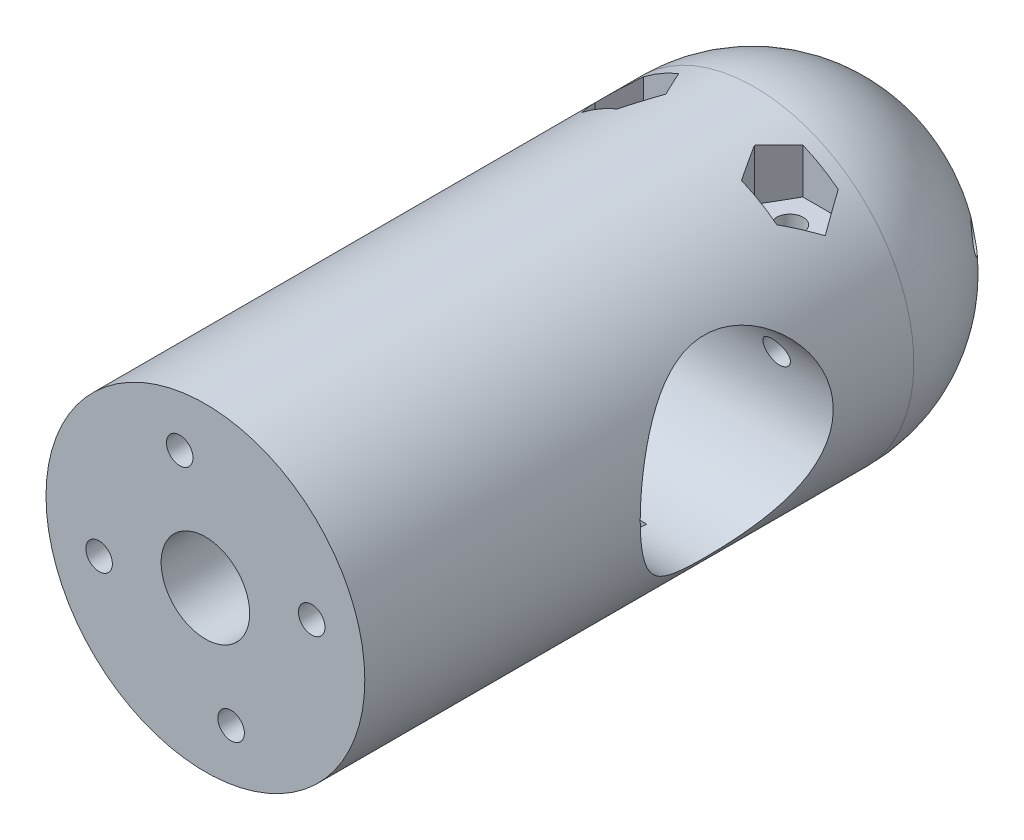
SolidWorks part; units mm, degrees
material "Custom Plastic"
ref_plane "Front Plane" through (0, 0, 0) normal (0, 0, 1) x (1, 0, 0)
ref_plane "Top Plane" through (0, 0, 0) normal (0, 1, 0) x (1, 0, 0)
ref_plane "Right Plane" through (0, 0, 0) normal (1, 0, 0) x (0, 0, -1)
sketch "Sketch1" plane through (0, 0, 0) normal (0, 0, 1) x (1, 0, 0)
  circle A0 centre (0, 0) radius 18
  dimension "D1" = 36
extrude "Boss-Extrude1" add sketch "Sketch1" along normal blind 62 contours A0
sketch "Sketch10" plane through (0, 0, 0) normal (0, 0, -1) x (-1, 0, 0)
  circle A0 centre (0, 0) radius 18
extrude "Boss-Extrude2" add sketch "Sketch10" along normal blind 17.5
fillet "Fillet1" radius 17.5 1 edges at (-18, 0, -17.5)
sketch "Sketch3" plane through (0, 0, 0) normal (1, 0, 0) x (0, 0, -1)
  line L0 (0, 0) -> (-62, 0) construction
  line L1 (-62, 18) -> (-62, -18) construction
  circle A0 centre (-20, 0) radius 10.9
  dimension "D2" = 21.8
  dimension "D1" = 20
extrude "Cut-Extrude1" cut sketch "Sketch3" against normal through all and the other way through all
sketch "Sketch4" plane through (0, 0, 62) normal (0, 0, 1) x (1, 0, 0)
  line L0 (0, 18) -> (0, -18) construction
  line L1 (18, 0) -> (-18, 0) construction
  circle A1 centre (0, 0) radius 18 construction
  circle A7 centre (12.0047, 2.9) radius 1.5
  circle A8 centre (2.9, -12.0047) radius 1.5
  circle A9 centre (-12.0047, -2.9) radius 1.5
  circle A10 centre (-2.9, 12.0047) radius 1.5
  point P10 (0, 0)
  point P19 (0, 0)
  dimension "D2" = 12.35
  dimension "D1" = 3
  dimension "D4" = 4
  dimension "D3" = 2.9
extrude "Cut-Extrude3" cut sketch "Sketch4" against normal through all contours A7 | A10 | A9 | A8
ref_plane "Plane1" through (0, -17.5, 0) normal (0, -1, 0) x (-1, 0, 0)
sketch "Sketch5" plane through (0, 0, 0) normal (0, 1, 0) x (1, 0, 0)
  line L1 (5, -5) -> (7, -8.4641)
  line L2 (7, -8.4641) -> (11, -8.4641)
  line L3 (11, -8.4641) -> (13, -5)
  line L4 (13, -5) -> (11, -1.5359)
  line L5 (11, -1.5359) -> (7, -1.5359)
  line L6 (7, -1.5359) -> (5, -5)
  line L7 (0, 0) -> (0, -62) construction
  line L8 (-18, -62) -> (18, -62) construction
  line L9 (-7, -1.5359) -> (-5, -5)
  line L10 (-11, -1.5359) -> (-7, -1.5359)
  line L11 (-13, -5) -> (-11, -1.5359)
  line L12 (-11, -8.4641) -> (-13, -5)
  line L13 (-7, -8.4641) -> (-11, -8.4641)
  line L14 (-5, -5) -> (-7, -8.4641)
  line L15 (0.5, 17.5) -> (-0.5, 17.5) construction
  circle A0 centre (9, -5) radius 4 construction
  circle A1 centre (-9, -5) radius 4 construction
  dimension "D1" = 8
  dimension "D2" = 22.5
  dimension "D3" = 9
extrude "Cut-Extrude7" cut sketch "Sketch5" against normal blind 6 from offset 17.5 contours L2 L3 L4 L5 L6 L1 | L13 L12 L11 L10 L9 L14
sketch "Sketch6" plane through (0, -17.5, 0) normal (0, -1, 0) x (-1, 0, 0)
  circle A0 centre (-9, -5) radius 1.5
  circle A1 centre (9, -5) radius 1.5
  dimension "D1" = 3
  dimension "D2" = 3
extrude "Cut-Extrude8" cut sketch "Sketch6" against normal through all and the other way through all
sketch "Sketch7" plane through (0, -17.5, 0) normal (0, -1, 0) x (-1, 0, 0)
  circle A0 centre (-9, -5) radius 4.05
  circle A1 centre (9, -5) radius 4.05
  dimension "D1" = 8.1
  dimension "D2" = 8.1
extrude "Cut-Extrude9" cut sketch "Sketch7" against normal blind 6
sketch "Sketch8" plane through (0, 0, 62) normal (0, 0, 1) x (1, 0, 0)
  circle A0 centre (2.9, -12.0047) radius 5
  circle A1 centre (-12.0047, -2.9) radius 5
  circle A2 centre (-2.9, 12.0047) radius 5
  circle A3 centre (12.0047, 2.9) radius 5
  point P12 (0, 0)
  dimension "D1" = 4
extrude "Cut-Extrude10" cut sketch "Sketch8" against normal blind 27.0638 from offset 15 offset against normal yes
sketch "Sketch9" plane through (0, 0, 62) normal (0, 0, 1) x (1, 0, 0)
  circle A0 centre (0, 0) radius 5
extrude "Cut-Extrude11" cut sketch "Sketch9" against normal blind 10
